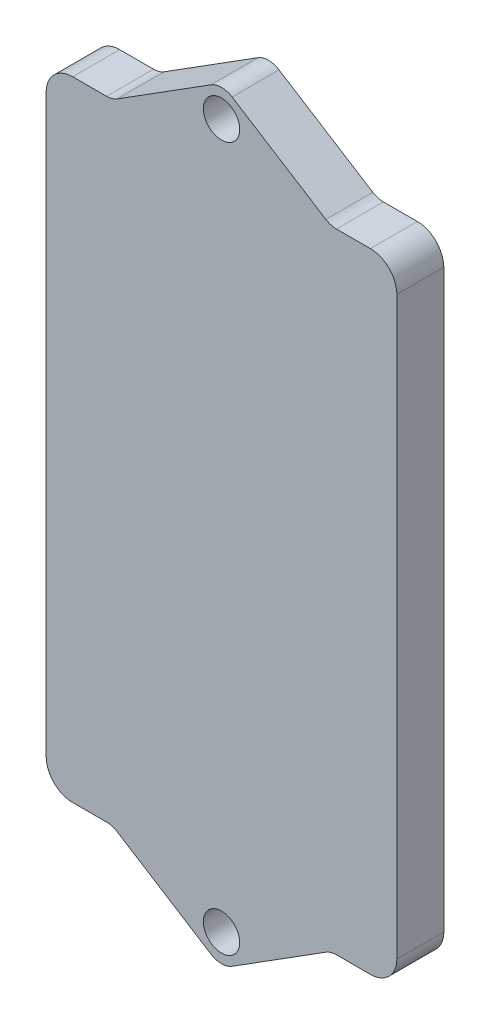
SolidWorks part; units mm, degrees
ref_plane "Plan de face" through (0, 0, 0) normal (0, 0, 1) x (1, 0, 0)
ref_plane "Plan de dessus" through (0, 0, 0) normal (0, 1, 0) x (1, 0, 0)
ref_plane "Plan de droite" through (0, 0, 0) normal (1, 0, 0) x (0, 0, -1)
sketch "Esquisse1" plane through (0, 0, 0) normal (0, 0, 1) x (1, 0, 0)
  line L0 (10, 95) -> (26.5, 105.4)
  line L1 (0, 0) -> (10, 0)
  line L2 (0, 0) -> (0, 95)
  line L3 (0, 95) -> (10, 95)
  line L4 (53, 0) -> (53, 95)
  line L5 (26.5, 105.4) -> (43, 95)
  line L7 (10, 0) -> (26.5, -10.4)
  line L8 (26.5, -10.4) -> (43, 0)
  line L9 (43, 95) -> (53, 95)
  line L10 (43, 0) -> (53, 0)
  circle A0 centre (26.5, 100.71) radius 2.75
  circle A1 centre (26.5, -5.71) radius 2.75
  point P15 (0, 0)
  point P16 (5, 0)
  dimension "D9" = 5.5
  dimension "D10" = 5.5
  dimension "D1" = 53
  dimension "D2" = 95
  dimension "D3" = 10
  dimension "D4" = 10
  dimension "D5" = 10.4
  dimension "D6" = 10.4
  dimension "D7" = 26.5
  dimension "D8" = 26.5
  dimension "D11" = 5.71
  dimension "D12" = 5.71
extrude "Boss.-Extru.1" add sketch "Esquisse1" along normal blind 7.1
fillet "Congé1" radius 3 6 edges at (43, 0, 3.55) (10, 0, 3.55) (10, 95, 3.55) (43, 95, 3.55) (26.5, -10.4, 3.55) (26.5, 105.4, 3.55)
fillet "Congé2" radius 4 4 edges at (0, 95, 3.55) (53, 95, 3.55) (53, 0, 3.55) (0, 0, 3.55)
sketch "Esquisse2" plane through (0, 0, 7.1) normal (0, 0, 1) x (1, 0, 0)
  line L0 (26.5, -8.46) -> (26.5, 103.46) construction
  circle A0 centre (26.5, -5.71) radius 2.75 construction
  circle A1 centre (26.5, 100.71) radius 2.75 construction
